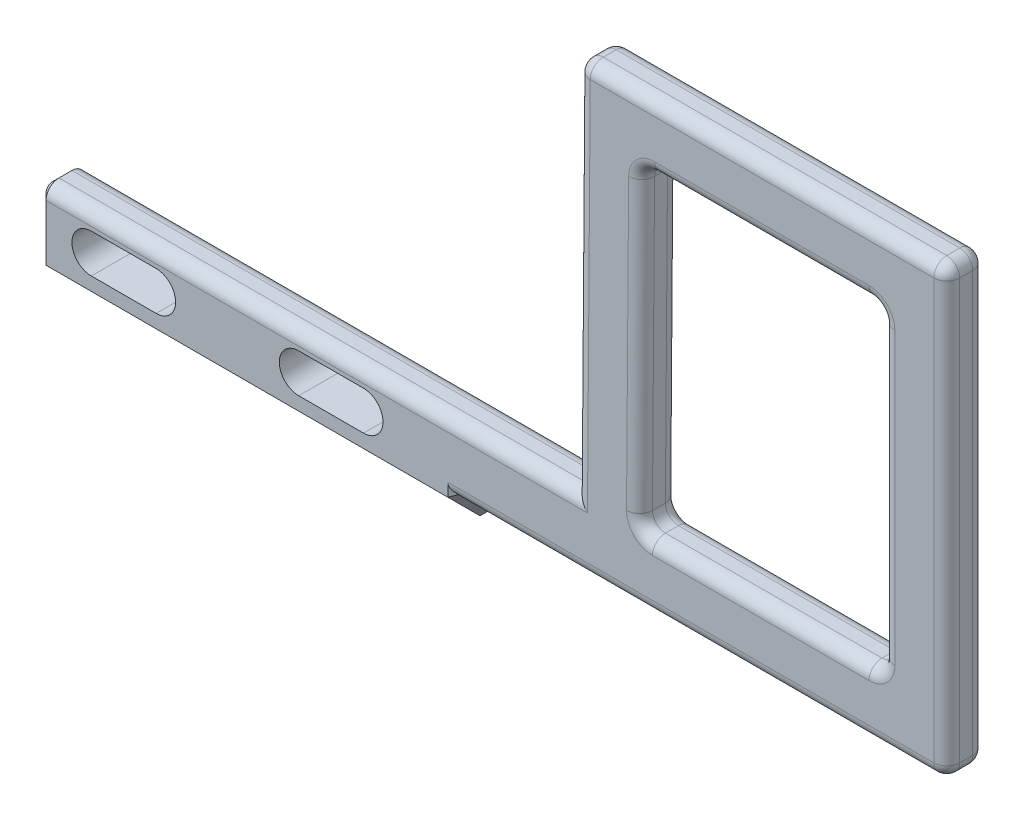
SolidWorks part; units mm, degrees
ref_plane "Plano frontal" through (0, 0, 0) normal (0, 0, 1) x (1, 0, 0)
ref_plane "Plano superior" through (0, 0, 0) normal (0, 1, 0) x (1, 0, 0)
ref_plane "Plano direito" through (0, 0, 0) normal (1, 0, 0) x (0, 0, -1)
sketch "Esboço1" plane through (0, 0, 0) normal (0, 0, 1) x (1, 0, 0)
  line L0 (6.1061, 19.1675) -> (34.6061, 19.1675) construction
  line L1 (5.8937, -9.9005) -> (6.1061, 19.1675)
  line L2 (6.1061, 19.1675) -> (34.6061, 19.1675)
  line L3 (34.6061, 19.1675) -> (34.6061, -15.2325)
  line L4 (-35.3939, -9.8994) -> (-35.3939, -15.2325)
  line L5 (-35.3939, -15.2325) -> (34.6061, -15.2325)
  line L6 (-35.3939, -9.8994) -> (5.8937, -9.9005)
  line L7 (10.8914, -10.2325) -> (11.0697, 14.1675)
  line L8 (11.0697, 14.1675) -> (29.6061, 14.1675)
  line L9 (-31.3939, -12.7015) -> (-26.3939, -12.7015) construction
  line L10 (-31.3939, -11.2015) -> (-26.3939, -11.2015)
  line L11 (-31.3939, -14.2015) -> (-26.3939, -14.2015)
  line L12 (-15.3939, -12.7015) -> (-10.3939, -12.7015) construction
  line L13 (-15.3939, -11.2015) -> (-10.3939, -11.2015)
  line L14 (-15.3939, -14.2015) -> (-10.3939, -14.2015)
  line L15 (29.6061, 14.1675) -> (29.6061, -10.2325)
  line L16 (10.8914, -10.2325) -> (29.6061, -10.2325)
  line L17 (34.6061, -12.8325) -> (34.6061, -15.2325)
  line L18 (49.6756, 19.1675) -> (34.6061, 19.1675) construction
  line L19 (58.385, -12.8325) -> (34.6061, -12.8325) construction
  line L20 (10.8936, -9.937) -> (11.0697, 14.1675) construction
  line L21 (-35.3939, -10.2325) -> (29.6061, -10.2325) construction
  circle A0 centre (-12.8939, -12.7015) radius 1.25
  circle A1 centre (-28.8939, -12.7015) radius 1.25
  arc A2 (-31.3939, -11.2015) -> (-31.3939, -14.2015) centre (-31.3939, -12.7015) ccw
  arc A3 (-26.3939, -14.2015) -> (-26.3939, -11.2015) centre (-26.3939, -12.7015) ccw
  arc A4 (-15.3939, -11.2015) -> (-15.3939, -14.2015) centre (-15.3939, -12.7015) ccw
  arc A5 (-10.3939, -14.2015) -> (-10.3939, -11.2015) centre (-10.3939, -12.7015) ccw
  point P18 (-28.8939, -12.7015)
  point P23 (-12.8939, -12.7015)
  dimension "D2" = 70
  dimension "D3" = 28.5
  dimension "D4" = 2.5
  dimension "D5" = 5
  dimension "D6" = 5
  dimension "D7" = 2.5
  dimension "D8" = 3
  dimension "D9" = 3
  dimension "D10" = 6.5
  dimension "D11" = 16
  dimension "D12" = 5
extrude "Ressalto-extrusão1" add sketch "Esboço1" along normal blind 3 contours L6 L4 L5 L3 L2 L1 A1 A0 region at (6.7798, 4.6278, 0)
sketch "Esboço2" plane through (-35.3939, 0, 0) normal (-1, 0, 0) x (0, 0, 1)
  line L1 (0, -15.2325) -> (-2.4861, -17.7185)
  line L2 (3, -15.2325) -> (0.5139, -17.7185)
  line L5 (0, -15.2325) -> (3, -15.2325)
  line L13 (-2.4861, -17.7185) -> (0.5139, -17.7185)
extrude "Ressalto-extrusão2" add sketch "Esboço2" against normal blind 32
fillet "Filete1" radius 1 25 edges at (-14.7501, -9.8999, 3) (-14.7501, -9.8999, 0) (20.3379, 14.1675, 3) (20.3379, 14.1675, 0) (20.2488, -10.2325, 3) (20.2488, -10.2325, 0) (5.9999, 4.6335, 3) (5.9999, 4.6335, 0) (34.6061, -15.2325, 1.5) (34.6061, 1.9675, 3) (34.6061, 1.9675, 0) (34.6061, 19.1675, 1.5) (20.3561, 19.1675, 3) (6.1061, 19.1675, 1.5) (20.3561, 19.1675, 0) (10.8914, -10.2325, 1.5) (10.9806, 1.9675, 3) (11.0697, 14.1675, 1.5) (10.9806, 1.9675, 0) (29.6061, 14.1675, 1.5) (29.6061, 1.9675, 3) (29.6061, -10.2325, 1.5) (29.6061, 1.9675, 0) (15.6061, -15.2325, 0) (15.6061, -15.2325, 3) tangent propagation no
chamfer "Chanfro1" distance 0.5 angle 45 13 edges at (-35.3939, -9.8994, 1.5) (-3.3939, -14.7325, 3) (-3.3939, -14.7325, 0) (-3.3939, -16.4755, -1.243) (-3.3939, -17.7185, -0.9861) (-3.3939, -16.4755, 1.757) (-35.3939, -13.0659, 0) (-35.3939, -16.4755, -1.243) (-35.3939, -17.7185, -0.9861) (-35.3939, -16.4755, 1.757) (-35.3939, -13.0659, 3) (-35.3939, -10.1923, 0.2929) (-35.3939, -10.1923, 2.7071) first distance on face at (-35.3939, -13.3857, 0.8785) first distance on face at (-3.3939, -15.6557, 0.8785)
fillet "Filete10" radius 0.4 1 edges at (-19.3939, -17.7185, -2.4861)
